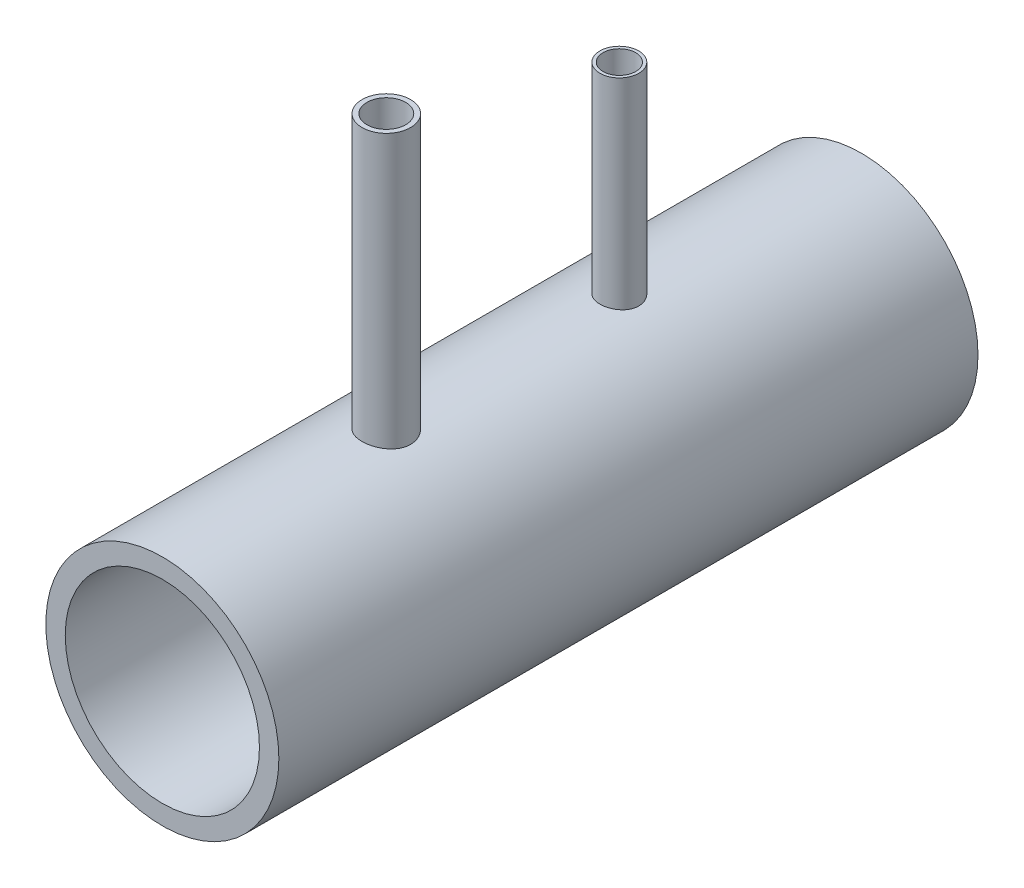
SolidWorks part; units mm, degrees
ref_plane "Front Plane" through (0, 0, 0) normal (0, 0, 1) x (1, 0, 0)
ref_plane "Top Plane" through (0, 0, 0) normal (0, 1, 0) x (1, 0, 0)
ref_plane "Right Plane" through (0, 0, 0) normal (1, 0, 0) x (0, 0, -1)
sketch "Sketch3" plane through (0, 0, 0) normal (0, 0, 1) x (1, 0, 0)
  circle A0 centre (0, 0) radius 38.1
  circle A1 centre (0, 0) radius 31.75
  dimension "D1" = 76.2
  dimension "D2" = 63.5
extrude "Boss-Extrude2" add sketch "Sketch3" along normal blind 228.6
sketch "Sketch5" plane through (0, 0, 0) normal (0, 1, 0) x (1, 0, 0)
  line L0 (-31.75, 0) -> (31.75, 0) construction
  circle A0 centre (0, -79.1683) radius 6.35
  circle A1 centre (0, -155.3683) radius 6.35
  dimension "D2" = 12.7
  dimension "D3" = 79.1683
  dimension "D1" = 76.2
extrude "Cut-Extrude3" cut sketch "Sketch5" along normal through all
extrude "Extrude-Thin1" add sketch "Sketch5<3>" against normal up to next from offset 127 separate body thin contours A1 thin type one direction wall 1.5875
sketch "Sketch5<3>" plane through (0, 0, 0) normal (0, 1, 0) x (1, 0, 0) same geometry as "Sketch5"
sketch "Sketch7" plane through (0, 0, 0) normal (1, 0, 0) x (0, 0, -1)
  line L0 (-79.1683, 0) -> (-79.1683, 103.4732)
  line L1 (-79.1683, 0) -> (-118.7419, 0)
  line L2 (41.91, 0) -> (-41.91, 0) construction
  point P3 (-79.1683, 13.8426)
  point P5 (-79.1683, 11.2834)
ref_plane "Plane1" through (0, 103.4732, 79.1683) normal (0, 1, 0) x (1, 0, 0)
sketch "Sketch8" plane through (0, 103.4732, 79.1683) normal (0, 1, 0) x (1, 0, 0)
  circle A0 centre (0, 0) radius 6.35 construction
  circle A1 centre (0, 0) radius 6.35
sweep "Sweep-Thin1" add profiles "Sketch8" path "Sketch7" parameters "D1"=1
